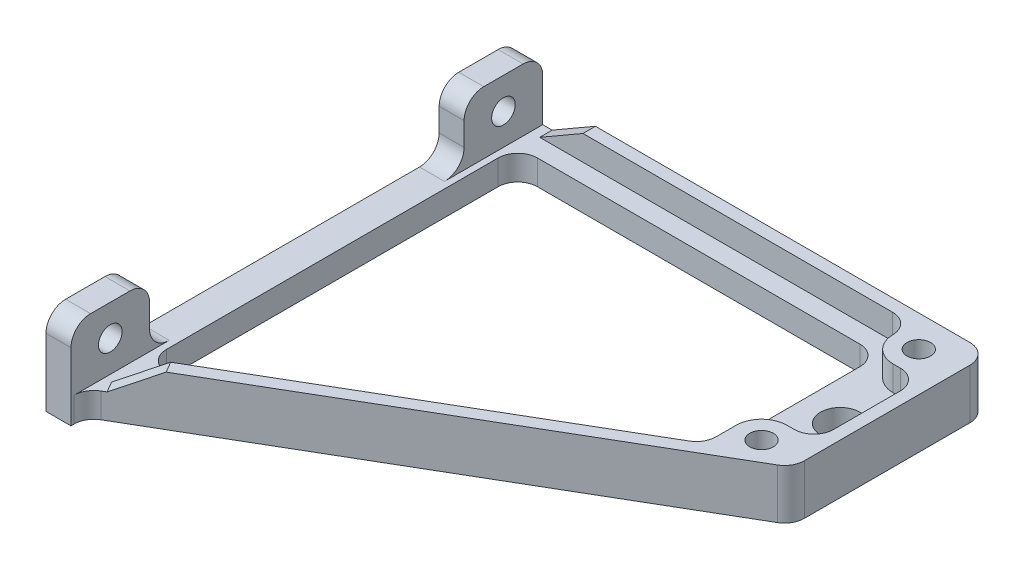
SolidWorks part; units mm, degrees
ref_plane "Front Plane" through (0, 0, 0) normal (0, 0, 1) x (1, 0, 0)
ref_plane "Top Plane" through (0, 0, 0) normal (0, 1, 0) x (1, 0, 0)
ref_plane "Right Plane" through (0, 0, 0) normal (1, 0, 0) x (0, 0, -1)
sketch "Sketch1" plane through (0, 0, 0) normal (0, 1, 0) x (1, 0, 0)
  line L0 (0, 0) -> (120, 0)
  line L1 (120, 0) -> (120, -50)
  line L2 (120, -50) -> (6.35, -116.2958)
  line L3 (0, -120) -> (0, 0)
  line L4 (110, 0) -> (110, -55.8333) construction
  line L5 (0, -120) -> (6.35, -120)
  line L6 (6.35, -120) -> (6.35, -116.2958)
  line L7 (6.35, -116.2958) -> (0, -120) construction
  dimension "D1" = 50
  dimension "D2" = 110
  dimension "D3" = 10
  dimension "D4" = 120
  dimension "D5" = 6.35
extrude "Boss-Extrude1" add sketch "Sketch1" along normal blind 6.35
sketch "Sketch2" plane through (0, 6.35, 0) normal (0, 1, 0) x (1, 0, 0)
  line L0 (110, -8) -> (110, -48) construction
  line L1 (100, -8) -> (100, -52.405)
  line L2 (100, -8) -> (8, -8)
  line L3 (8, -8) -> (8, -106.0717)
  line L4 (8, -106.0717) -> (100, -52.405)
  line L7 (0, 0) -> (0, -120)
  line L8 (0, -120) -> (6.35, -120)
  line L9 (6.35, -120) -> (6.35, -116.2958)
  line L10 (6.35, -116.2958) -> (120, -50)
  line L11 (120, -50) -> (120, 0)
  line L12 (120, 0) -> (0, 0)
  line L13 (0, 0) -> (0, -120)
  line L14 (0, -120) -> (6.35, -120)
  line L15 (6.35, -120) -> (6.35, -116.2958)
  line L16 (6.35, -116.2958) -> (120, -50)
  line L17 (120, -50) -> (120, 0)
  line L18 (120, 0) -> (0, 0)
  circle A0 centre (110, -8) radius 3
  circle A1 centre (110, -48) radius 3
  dimension "D4" = 6
  dimension "D1" = 40
  dimension "D2" = 110
  dimension "D3" = 8
  dimension "D6" = 8
  dimension "D7" = 8
  dimension "D8" = 8
  dimension "D5" = 0
extrude "Cut-Extrude3" cut sketch "Sketch2" against normal through all contours L1 L4 L3 L2 | A0 | A1
sketch "Sketch7" plane through (0, 6.35, 0) normal (0, 1, 0) x (1, 0, 0)
  line L0 (4.7502, -113.5533) -> (116.825, -48.1764)
  line L1 (116.825, -48.1764) -> (116.825, -3.175)
  line L2 (116.825, -3.175) -> (4.7502, -3.175)
  line L3 (4.7502, -113.5533) -> (6.35, -116.2958)
  line L4 (3.175, -116.825) -> (3.175, -116.825)
  line L5 (4.7502, -3.175) -> (4.7502, 0)
  line L6 (0, 0) -> (0, -120)
  line L7 (0, -120) -> (6.35, -120)
  line L8 (6.35, -120) -> (6.35, -116.2958)
  line L9 (6.35, -116.2958) -> (120, -50)
  line L10 (120, -50) -> (120, 0)
  line L11 (120, 0) -> (0, 0)
  line L12 (0, 0) -> (0, -120)
  line L13 (0, -120) -> (6.35, -120)
  line L14 (6.35, -120) -> (6.35, -116.2958)
  line L15 (6.35, -116.2958) -> (120, -50)
  line L16 (120, -50) -> (120, 0)
  line L17 (120, 0) -> (0, 0)
  line L18 (116.825, -3.175) -> (3.175, -3.175) construction
  line L20 (3.175, -3.175) -> (3.175, -116.825) construction
  line L21 (3.175, -116.825) -> (3.175, -114.4722) construction
  line L22 (3.175, -114.4722) -> (116.825, -48.1764) construction
  point P12 (0, 0)
  line M16 (6.35, -116.2958) -> (120, -50)
  line M17 (120, -50) -> (120, 0)
  line M18 (120, 0) -> (0, 0)
  dimension "D1" = 0
  dimension "D2" = 3.175
extrude "Boss-Extrude3" add sketch "Sketch7" along normal blind 6.35 contours L5 L2 L1 L0 M16 M17 M18 region at (61.6126, 6.35, 82.2791)
chamfer "Chamfer1" distance 15 angle 30 2 edges at (5.5501, 12.7, 114.9246) (4.7502, 12.7, 1.5875) first distance on face at (61.7813, 12.7, 41.7969)
sketch "Sketch8" plane through (0, 6.35, 0) normal (0, 1, 0) x (1, 0, 0)
  line L0 (110, -14.5) -> (116.825, -14.5)
  line L1 (116.825, -48.1764) -> (116.825, -3.175) construction
  line L2 (103.5, -8) -> (103.5, -3.175)
  line L3 (116.825, -3.175) -> (8.7517, -3.175) construction
  line L4 (103.5, -3.175) -> (116.825, -3.175)
  line L5 (116.825, -3.175) -> (116.825, -14.5)
  line L6 (110, -41.5) -> (116.825, -41.5)
  line L7 (103.5, -48) -> (103.5, -55.9493)
  line L8 (8.2066, -111.5371) -> (116.825, -48.1764) construction
  line L9 (116.825, -41.5) -> (116.825, -48.1764)
  line L10 (116.825, -48.1764) -> (103.5, -55.9493)
  circle A0 centre (110, -48) radius 3 construction
  circle A1 centre (110, -8) radius 3 construction
  circle A2 centre (110, -48) radius 3
  circle A3 centre (110, -8) radius 3
  arc A4 (103.5, -8) -> (110, -14.5) centre (110, -8) ccw
  arc A5 (110, -41.5) -> (103.5, -48) centre (110, -48) ccw
  dimension "D1" = 3.5
extrude "Boss-Extrude4" add sketch "Sketch8" along normal blind 6.35
sketch "Sketch9" plane through (0, 6.35, 0) normal (0, 1, 0) x (1, 0, 0)
  line L0 (6.35, -120) -> (6.35, -116.2958) construction
  line L1 (0, 0) -> (6.35, 0)
  line L2 (0, 0) -> (0, -20)
  line L3 (0, -20) -> (6.35, -20)
  line L4 (6.35, 0) -> (6.35, -20)
  line L5 (0, -120) -> (6.35, -120)
  line L6 (0, -120) -> (0, -100)
  line L7 (0, -100) -> (6.35, -100)
  line L8 (6.35, -120) -> (6.35, -100)
  dimension "D1" = 20
extrude "Boss-Extrude5" add sketch "Sketch9" along normal blind 15.875
sketch "Sketch10" plane through (6.35, 0, 0) normal (1, 0, 0) x (0, 0, -1)
  line L0 (-20, 22.225) -> (0, 6.35) construction
  line L1 (-120, 22.225) -> (-100, 6.35) construction
  circle A0 centre (-10, 14.2875) radius 3
  circle A1 centre (-110, 14.2875) radius 3
  dimension "D1" = 6
extrude "Cut-Extrude4" cut sketch "Sketch10" against normal blind 110.875
fillet "Fillet3" radius 5 17 edges at (103.5, 9.525, 55.9493) (116.825, 9.525, 41.5) (116.825, 9.525, 14.5) (103.5, 9.525, 3.175) (120, 6.35, 0) (120, 6.35, 50) (6.35, 3.175, 116.2958) (8, 3.175, 106.0717) (100, 3.175, 52.405) (100, 3.175, 8) (8, 3.175, 8) (3.175, 22.225, 120) (3.175, 6.35, 100) (3.175, 22.225, 100) (3.175, 22.225, 0) (3.175, 22.225, 20) (3.175, 6.35, 20)
sketch "Sketch11" plane through (0, 6.35, 0) normal (0, 1, 0) x (1, 0, 0)
  line L0 (110, -8) -> (110, -48) construction
  circle A0 centre (110, -28) radius 5
  dimension "D1" = 10
extrude "Cut-Extrude5" cut sketch "Sketch11" against normal blind 15.875
